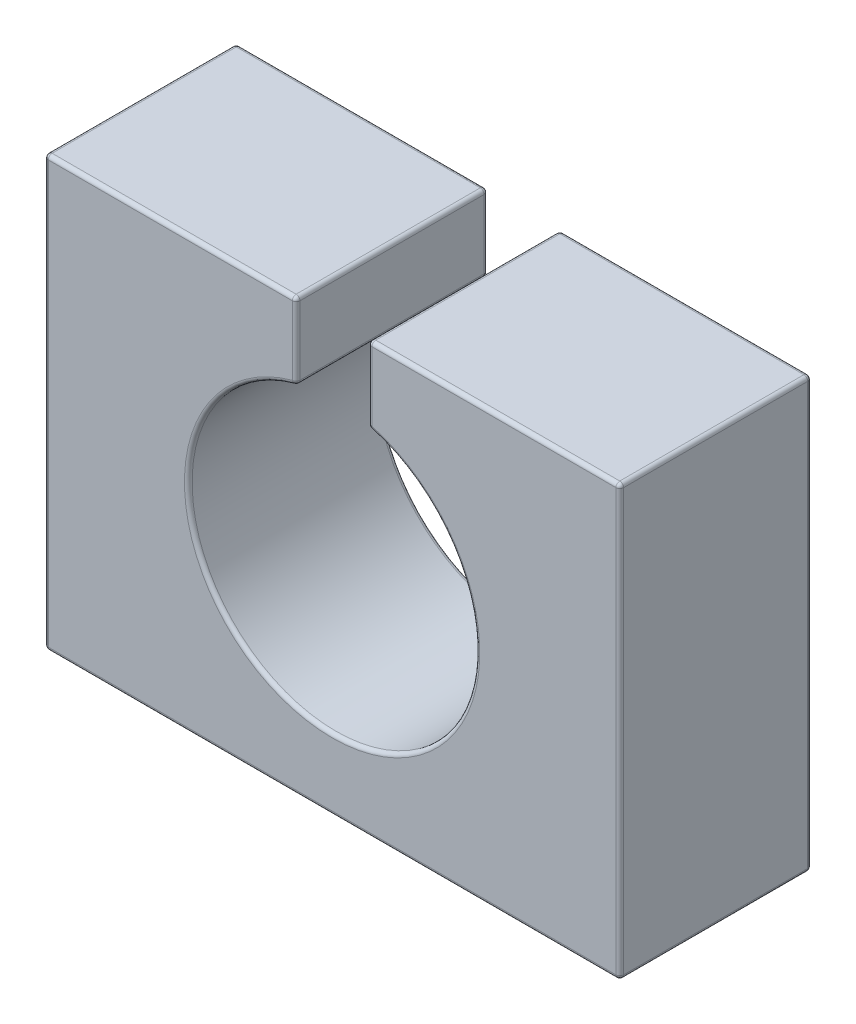
SolidWorks part; units mm, degrees
ref_plane "Front Plane" through (0, 0, 0) normal (0, 0, 1) x (1, 0, 0)
ref_plane "Top Plane" through (0, 0, 0) normal (0, 1, 0) x (1, 0, 0)
ref_plane "Right Plane" through (0, 0, 0) normal (1, 0, 0) x (0, 0, -1)
sketch "Sketch1" plane through (0, 0, 0) normal (0, 0, 1) x (1, 0, 0)
  line L0 (0, 0) -> (38.1, 0)
  line L1 (38.1, 0) -> (38.1, 28.448)
  line L7 (0, 28.448) -> (0, 0)
  line L8 (19.05, 0) -> (19.05, 36.1275) construction
  line L9 (0, 28.448) -> (38.1, 28.448)
  dimension "D1" = 28.448
  dimension "D3" = 38.1
extrude "Boss-Extrude1" add sketch "Sketch1" against normal blind 12.7
sketch "Sketch3" plane through (0, 0, 0) normal (0, 0, 1) x (1, 0, 0)
  line L0 (19.05, 0) -> (19.05, 28.9356) construction
  line L1 (0, 0) -> (38.1, 0) construction
  line L2 (16.6687, 28.448) -> (16.6688, 23.4465)
  line L3 (38.1, 28.448) -> (0, 28.448) construction
  line L4 (16.6687, 28.448) -> (21.4312, 28.448)
  line L5 (21.4312, 28.448) -> (21.4312, 23.4465)
  line L6 (16.6687, 28.448) -> (21.4312, 28.448)
  line L7 (0, 28.448) -> (0, 0) construction
  arc A0 (16.6688, 23.4465) -> (21.4312, 23.4465) centre (19.05, 14.224) ccw
  line M8 (38.1, 28.448) -> (0, 28.448)
  dimension "D1" = 19.05
  dimension "D2" = 14.224
  dimension "D3" = 4.7625
  dimension "D4" = 16.6687
extrude "Cut-Extrude2" cut sketch "Sketch3" against normal up to next contours A0 L0 L6 L2 | L0 A0 L5 M8 region at (15.2183, 15.1017, 0) region at (22.8817, 15.1017, 0)
fillet "Fillet1" radius 0.254 24 edges at (21.4312, 25.9473, -12.7) (21.4312, 28.448, -6.35) (29.7656, 28.448, -12.7) (38.1, 28.448, -6.35) (38.1, 14.224, -12.7) (21.4312, 25.9473, 0) (29.7656, 28.448, 0) (38.1, 14.224, 0) (8.3344, 28.448, 0) (8.3344, 28.448, -12.7) (0, 14.224, -12.7) (0, 28.448, -6.35) (0, 14.224, 0) (38.1, 0, -6.35) (19.05, 0, -12.7) (0, 0, -6.35) (19.05, 0, 0) (21.4312, 23.4465, -6.35) (19.05, 4.699, 0) (19.05, 4.699, -12.7) (16.6688, 23.4465, -6.35) (16.6688, 25.9473, 0) (16.6687, 28.448, -6.35) (16.6687, 25.9473, -12.7)
